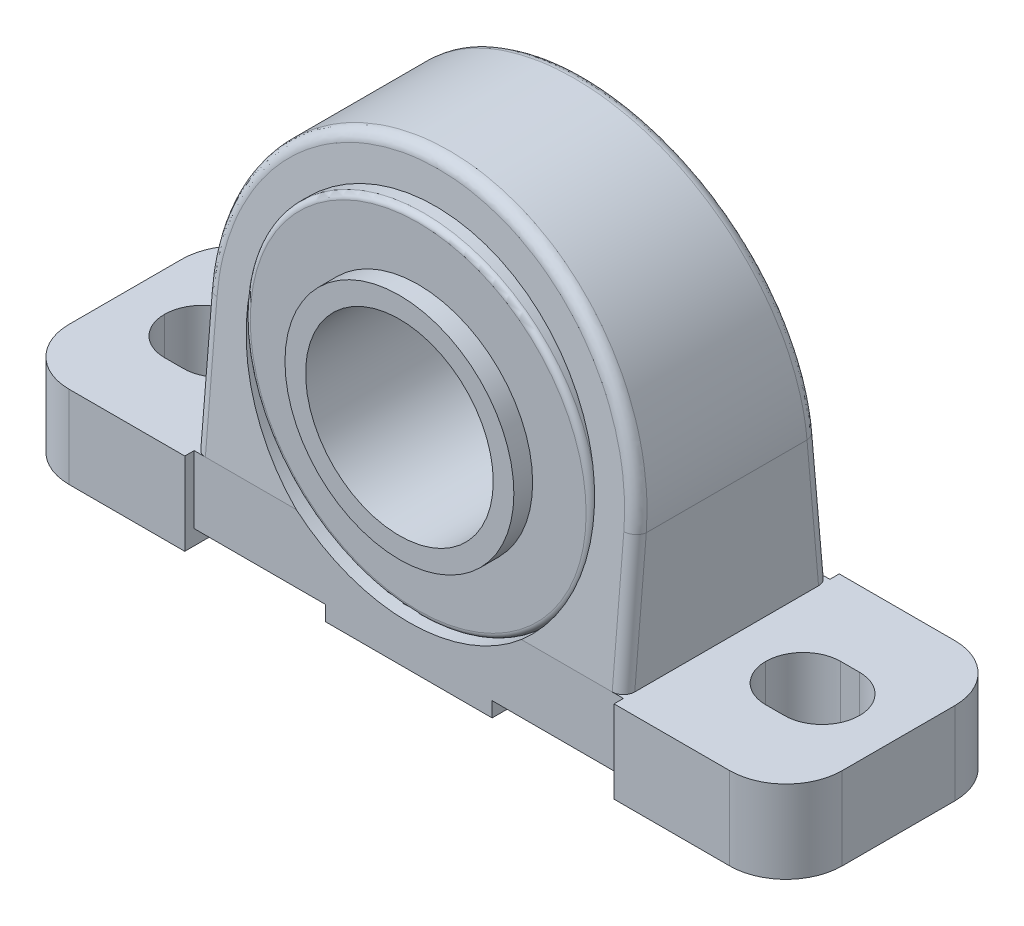
SolidWorks part; units mm, degrees
material "Ferro fundido cinza (SN)"
ref_plane "Plano frontal" through (0, 0, 0) normal (0, 0, 1) x (1, 0, 0)
ref_plane "Plano superior" through (0, 0, 0) normal (0, 1, 0) x (1, 0, 0)
ref_plane "Plano direito" through (0, 0, 0) normal (1, 0, 0) x (0, 0, -1)
sketch "Esboço1" plane through (0, 0, 0) normal (0, 1, 0) x (1, 0, 0)
  line L1 (-103, 30) -> (103, 30)
  line L2 (-103, 30) -> (-103, -30)
  line L3 (-103, -30) -> (103, -30)
  line L4 (103, 30) -> (103, -30)
  line L5 (-103, 30) -> (103, -30) construction
  line L6 (-103, -30) -> (103, 30) construction
  point P0 (0, 0)
  dimension "D1" = 206
  dimension "D2" = 60
extrude "Ressalto-extrusão1" add sketch "Esboço1" along normal blind 22
sketch "Esboço2" plane through (0, 0, 0) normal (0, 0, 1) x (1, 0, 0)
  line L0 (-57.2, 57.2) -> (-57.2, 8.6404)
  line L1 (-57.2, 8.6404) -> (57.2, 8.6404)
  line L2 (57.2, 8.6404) -> (57.2, 57.2)
  circle A0 centre (0, 57.2) radius 25
  arc A1 (57.2, 57.2) -> (-57.2, 57.2) centre (0, 57.2) ccw
  dimension "D2" = 50
  dimension "D1" = 57.2
extrude "Ressalto-extrusão2" add sketch "Esboço2" along normal mid plane 55
sketch "Esboço3" plane through (0, 0, 0) normal (0, -1, 0) x (1, 0, 0)
  line L0 (-57.2, 27.5) -> (57.2, 27.5)
  line L1 (57.2, 27.5) -> (57.2, 42.9454)
  line L2 (57.2, 42.9454) -> (-57.2, 42.9454)
  line L3 (-57.2, 42.9454) -> (-57.2, 27.5)
  line L4 (-57.2, -27.5) -> (57.2, -27.5)
  line L5 (57.2, -27.5) -> (57.2, -48.9231)
  line L6 (57.2, -48.9231) -> (-57.2, -48.9231)
  line L7 (-57.2, -48.9231) -> (-57.2, -27.5)
extrude "Corte-extrusão1" cut sketch "Esboço3" against normal through all
sketch "Esboço4" plane through (0, 0, 0) normal (1, 0, 0) x (0, 0, -1)
  line L0 (-27.5, 22) -> (-17.8011, 132.8586)
  line L1 (-17.8011, 132.8586) -> (17.8011, 132.8586)
  line L2 (17.8011, 132.8586) -> (27.5, 22)
  line L3 (-27.5, 114.4) -> (-27.5, 57.2) construction
  line L5 (27.5, 22) -> (27.5, 57.2) construction
  line L6 (-27.5, 22) -> (-69.0263, 22)
  line L7 (-69.0263, 22) -> (-69.0263, 153.9019)
  line L8 (-69.0263, 153.9019) -> (74.2358, 153.9019)
  line L9 (74.2358, 153.9019) -> (74.2358, 22)
  line L10 (74.2358, 22) -> (27.5, 22)
  dimension "D1" = 5
  dimension "D2" = 5
extrude "Corte-extrusão2" cut sketch "Esboço4" against normal mid plane 150
sketch "Esboço5" plane through (0, 0, 0) normal (0, 0, 1) x (1, 0, 0)
  circle A0 centre (0, 57.2) radius 25
  circle A1 centre (0, 57.2) radius 30.5
  dimension "D1" = 5.5
extrude "Ressalto-extrusão3" add sketch "Esboço5" along normal mid plane 60
sketch "Esboço6" plane through (0, 0, 0) normal (0, 0, 1) x (1, 0, 0)
  circle A0 centre (0, 57.2) radius 46.25
  circle A1 centre (0, 57.2) radius 30.5
  dimension "D1" = 92.5
extrude "Corte-extrusão3" cut sketch "Esboço6" against normal mid plane 60
sketch "Esboço7" plane through (0, 0, 0) normal (0, 0, 1) x (1, 0, 0)
  circle A0 centre (0, 57.2) radius 46.25
  circle A1 centre (0, 57.2) radius 30.5
extrude "Ressalto-extrusão4" add sketch "Esboço7" along normal mid plane 50
sketch "Esboço8" plane through (0, 0, 0) normal (1, 0, 0) x (0, 0, -1)
  line L0 (-20.374, 103.45) -> (-25, 103.45) construction
  line L1 (-25, 103.45) -> (-25, 50.5751) construction
  line L2 (25, 103.45) -> (20.374, 103.45) construction
  line L3 (25, 50.5751) -> (25, 103.45) construction
  line L4 (23.5, 103.45) -> (28.3872, 103.45)
  line L5 (28.3872, 103.45) -> (28.0726, 101.95)
  line L6 (28.0726, 101.95) -> (25, 101.95)
  line L7 (-23.5, 103.45) -> (-29.2242, 103.45)
  line L8 (-29.2242, 103.45) -> (-29.2242, 100.9652)
  line L9 (-29.2242, 100.9652) -> (-25, 101.95)
  line L10 (30, 57.2) -> (-41.9021, 57.2) construction
  line L11 (30, 26.7) -> (30, 87.7) construction
  arc A0 (-23.5, 103.45) -> (-25, 101.95) centre (-23.4513, 101.9013) ccw
  arc A1 (23.5, 103.45) -> (25, 101.95) centre (23.3089, 101.7589) cw
  dimension "D1" = 1.5
  dimension "D2" = 1.5
  dimension "D3" = 1.5
  dimension "D4" = 1.5
revolve "Corte-Revolução1" cut sketch "Esboço8" angle 360 about L10
fillet "Filete2" radius 3 6 edges at (57.2, 39.6, -25.9602) (-57.2, 39.6, -25.9602) (-57.2, 39.6, 25.9602) (57.2, 39.6, 25.9602) (0, 114.4, -19.416) (0, 114.4, 19.416)
sketch "Esboço9" plane through (0, 22, 0) normal (0, 1, 0) x (1, 0, 0)
  line L0 (103, 30) -> (57.2, 30) construction
  line L1 (77.5999, 10) -> (82.6001, 10)
  line L2 (67.6, 0.0001) -> (67.6, -0.0001)
  line L3 (77.5999, -10) -> (82.6001, -10)
  line L4 (92.6, 0.0001) -> (92.6, -0.0001)
  line L5 (67.6, 10) -> (92.6, -10) construction
  line L6 (67.6, -10) -> (92.6, 10) construction
  line L7 (103, -30) -> (103, 30) construction
  line L8 (0, 0) -> (0, -66.5417) construction
  line L9 (-67.6, -10) -> (-92.6, 10) construction
  line L10 (-67.6, 10) -> (-92.6, -10) construction
  line L11 (-92.6, 0.0001) -> (-92.6, -0.0001)
  line L12 (-77.5999, -10) -> (-82.6001, -10)
  line L13 (-67.6, 0.0001) -> (-67.6, -0.0001)
  line L14 (-77.5999, 10) -> (-82.6001, 10)
  arc A0 (82.6001, 10) -> (92.6, 0.0001) centre (82.6001, 0.0001) cw
  arc A1 (82.6001, -10) -> (92.6, -0.0001) centre (82.6001, -0.0001) ccw
  arc A2 (67.6, -0.0001) -> (77.5999, -10) centre (77.5999, -0.0001) ccw
  arc A3 (77.5999, 10) -> (67.6, 0.0001) centre (77.5999, 0.0001) ccw
  arc A4 (-77.5999, 10) -> (-67.6, 0.0001) centre (-77.5999, 0.0001) cw
  arc A5 (-67.6, -0.0001) -> (-77.5999, -10) centre (-77.5999, -0.0001) cw
  arc A6 (-82.6001, -10) -> (-92.6, -0.0001) centre (-82.6001, -0.0001) cw
  arc A7 (-82.6001, 10) -> (-92.6, 0.0001) centre (-82.6001, 0.0001) ccw
  point P0 (80.1, 0)
  point P7 (80.1, 30)
  point P10 (103, 0)
  point P42 (-80.1, 0)
  dimension "D5" = 9.9999
  dimension "D1" = 20
  dimension "D2" = 25
  dimension "D3" = 0
  dimension "D4" = 0
extrude "Corte-extrusão4" cut sketch "Esboço9" against normal through all
fillet "Filete3" radius 15 4 edges at (103, 11, -30) (103, 11, 30) (-103, 11, -30) (-103, 11, 30)
sketch "Esboço10" plane through (0, 0, 27.5) normal (0, 0, 1) x (1, 0, 0)
  line L0 (-57.2, 0) -> (57.2, 0) construction
  line L1 (-57.2, 0) -> (-22.2, 0)
  line L2 (-57.2, 0) -> (-57.2, 4)
  line L3 (-57.2, 4) -> (-22.2, 4)
  line L4 (-22.2, 0) -> (-22.2, 4)
  line L5 (-57.2, 0) -> (-57.2, 22) construction
  line L6 (0, 0) -> (0, -15.4534) construction
  line L7 (22.2, 0) -> (22.2, 4)
  line L8 (57.2, 4) -> (22.2, 4)
  line L9 (57.2, 0) -> (57.2, 4)
  line L10 (57.2, 0) -> (22.2, 0)
  dimension "D1" = 35
  dimension "D2" = 4
  dimension "D3" = 0
extrude "Corte-extrusão5" cut sketch "Esboço10" against normal through all
scale "Escala1" scale about centroid uniform scaling yes scale factor 0.5
